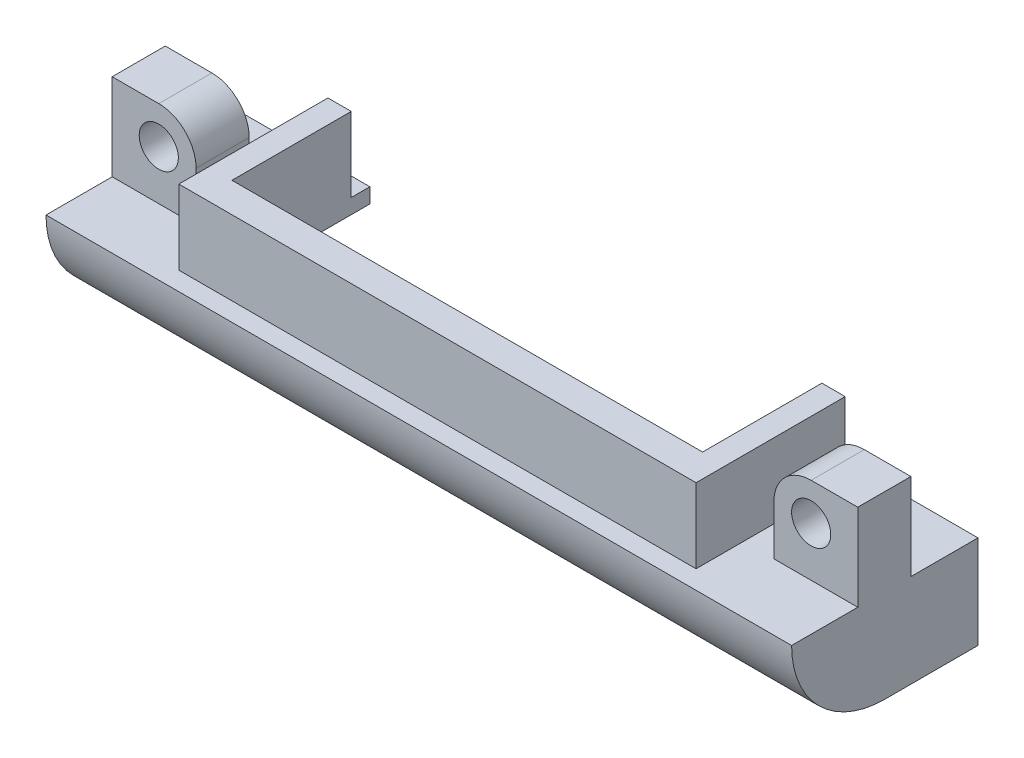
SolidWorks part; units mm, degrees
ref_plane "Front Plane" through (0, 0, 0) normal (0, 0, 1) x (1, 0, 0)
ref_plane "Top Plane" through (0, 0, 0) normal (0, 1, 0) x (1, 0, 0)
ref_plane "Right Plane" through (0, 0, 0) normal (1, 0, 0) x (0, 0, -1)
sketch "Sketch1" plane through (0, 0, 0) normal (1, 0, 0) x (0, 0, -1)
  line L0 (-10, 0) -> (0, 0)
  line L1 (0, 0) -> (0, -5)
  line L2 (0, -5) -> (-5, -5)
  line L3 (-10, 0) -> (-10, 3.6171) construction
  arc A0 (-5, -5) -> (-10, 0) centre (-5, 0) cw
  dimension "D1" = 10
  dimension "D2" = 5
extrude "Boss-Extrude1" add sketch "Sketch1" along normal mid plane 40
sketch "Sketch2" plane through (0, 0, 0) normal (0, 1, 0) x (1, 0, 0)
  line L1 (-13.875, -1) -> (13.875, -1)
  line L2 (-13.875, -1) -> (-13.875, -9)
  line L3 (-13.875, -9) -> (13.875, -9)
  line L4 (13.875, -1) -> (13.875, -9)
  line L5 (20, -10) -> (-20, -10) construction
  line L6 (0, 0) -> (0, -1) construction
  line L7 (20, 0) -> (-20, 0) construction
  dimension "D1" = 1
  dimension "D2" = 27.75
  dimension "D3" = 1
extrude "Boss-Extrude2" add sketch "Sketch2" along normal blind 4
sketch "Sketch4" plane through (0, 0, 0) normal (1, 0, 0) x (0, 0, -1)
  line L0 (0, -4.2) -> (-6.5564, -3.1616)
  line L1 (0, -5) -> (0, 0) construction
  line L2 (-7.4, -2.1739) -> (-7.4, 4)
  line L3 (-9, 4) -> (-1, 4) construction
  line L4 (-7.4, 4) -> (0, 4)
  line L5 (0, 4) -> (0, -4.2)
  line L6 (-5, -5) -> (0, -5) construction
  line L7 (-9, 4) -> (-9, 0) construction
  line L10 (-9, -0.8) -> (-1, -0.8)
  line L11 (-7.4, -0.8) -> (0, -0.8)
  arc A0 (-6.5564, -3.1616) -> (-7.4, -2.1739) centre (-6.4, -2.1739) cw
  dimension "D4" = 1
  dimension "D1" = 0.8
  dimension "D2" = 9
  dimension "D3" = 1.6
  dimension "D5" = 0.8
extrude "Cut-Extrude1" cut sketch "Sketch4" against normal offset from surface 1.25 and the other way offset from surface 1.25 contours L2 L11 L5 L4 | A0 L0 L5 L11 L2 region at (0, -2.2227, 3.4163) region at (0, 1.6, 3.7) up to face at (-13.875, 2, 5) other way up to face at (13.875, 2, 5)
sketch "Sketch6" plane through (0, 0, 0) normal (0, 1, 0) x (1, 0, 0)
  line L0 (-20, 0) -> (-20, -10) construction
  line L1 (-20, -3.6) -> (-15.5, -3.6)
  line L2 (-20, -3.6) -> (-20, -6.45)
  line L3 (-20, -6.45) -> (-15.5, -6.45)
  line L4 (-15.5, -3.6) -> (-15.5, -6.45)
  line L5 (-12.625, 0) -> (-20, 0) construction
  dimension "D1" = 3.6
  dimension "D2" = 2.85
  dimension "D3" = 4.5
extrude "Boss-Extrude3" add sketch "Sketch6" along normal blind 4.65
fillet "Fillet1" radius 2 1 edges at (-15.5, 4.65, 5.025)
sketch "Sketch7" plane through (0, 0, 3.6) normal (0, 0, -1) x (-1, 0, 0)
  line L0 (0, 0) -> (0, 7.5391) construction
  line L1 (17.5, 2.65) -> (15.5, 2.65) construction
  line L2 (15.5, 2.65) -> (15.5, 0) construction
  line L3 (17.523, 2.65) -> (17.5, 2.65) construction
  line L4 (17.5, 2.65) -> (17.5, 4.65) construction
  line L5 (17.5, 4.65) -> (20, 4.65) construction
  circle A0 centre (17.5, 2.65) radius 1.05
  dimension "D1" = 2.1
  dimension "D2" = 35
extrude "Cut-Extrude2" cut sketch "Sketch7" against normal up to next
mirror "Mirror1" about plane through (0, 0, 0) normal (1, 0, 0) of "Cut-Extrude2", "Fillet1", "Boss-Extrude3"
extrude "Cut-Extrude3" cut sketch "Sketch4<3>" against normal offset from surface 3.5 and the other way offset from surface 4.5 contours A0 L0 L5 L11 L2 region at (0, -2.2227, 3.4163) up to face at (-20, -0.2169, 4.5169) other way up to face at (20, -0.2169, 4.5169)
sketch "Sketch4<3>" plane through (0, 0, 0) normal (1, 0, 0) x (0, 0, -1) same geometry as "Sketch4"
shell "Shell1" thickness 1.1 removed face at (-0.1667, -1.8, 0)
